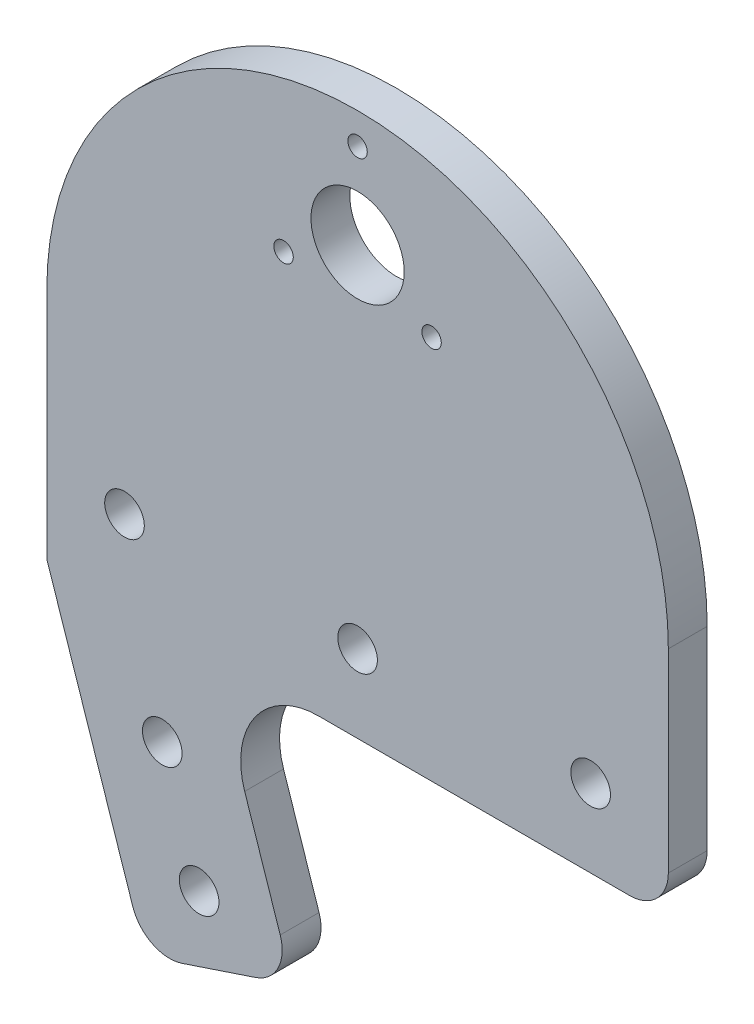
SolidWorks part; units mm, degrees
ref_plane "正面" through (0, 0, 0) normal (0, 0, 1) x (1, 0, 0)
ref_plane "平面" through (0, 0, 0) normal (0, 1, 0) x (1, 0, 0)
ref_plane "右側面" through (0, 0, 0) normal (1, 0, 0) x (0, 0, -1)
sketch "ｽｹｯﾁ1" plane through (0, 0, 0) normal (0, 0, 1) x (1, 0, 0)
  line L0 (-40, -55) -> (40, -55)
  line L1 (-40, -25) -> (-40, -55)
  line L2 (40, -25) -> (40, -55)
  line L3 (0, 0) -> (0, -25) construction
  line L4 (-30, -25) -> (-30, -45) construction
  line L5 (-30, -45) -> (30, -45) construction
  line L6 (30, -45) -> (30, -25) construction
  line L7 (-40, -25) -> (40, -25) construction
  circle A0 centre (0, 0) radius 6
  arc A2 (-40, -25) -> (40, -25) centre (0, -25) cw
  circle A3 centre (-30, -45) radius 2.55
  circle A4 centre (0, -45) radius 2.55
  circle A5 centre (30, -45) radius 2.55
  dimension "D1" = 80
  dimension "D2" = 12
  dimension "D3" = 30
  dimension "D4" = 25
  dimension "D8" = 5.1
  dimension "D5" = 10
  dimension "D6" = 10
  dimension "D7" = 10
extrude "ﾎﾞｽ - 押し出し1" add sketch "ｽｹｯﾁ1" along normal blind 5
sketch "ｽｹｯﾁ2" plane through (0, 0, 5) normal (0, 0, 1) x (1, 0, 0)
  line L0 (-27.3509, -92.9473) -> (-40, -55)
  line L1 (-37.8918, -61.3246) -> (0.0555, -175.1666) construction
  line L2 (-27.3509, -92.9473) -> (-8.3772, -86.6228)
  line L3 (-18.9181, -55) -> (19.0292, -168.842) construction
  line L4 (-8.3772, -86.6228) -> (-18.9181, -55)
  line L5 (-40, -55) -> (40, -55) construction
  line L6 (-18.9181, -55) -> (-20.3412, -55.4743) construction
  line L7 (-18.9181, -55) -> (-40, -55)
  line L8 (-17.8641, -89.7851) -> (-29.4591, -55) construction
  circle A0 centre (-20.3939, -82.1956) radius 2.55
  circle A1 centre (-25.1373, -67.9653) radius 2.55
  dimension "D1" = 8
  dimension "D2" = 5.1
  dimension "D4" = 15
  dimension "D3" = 40
extrude "ﾎﾞｽ - 押し出し2" add sketch "ｽｹｯﾁ2" against normal up to surface (5 mm away) up to face at (-27.45, -45, 0)
fillet "ﾌｨﾚｯﾄ1" radius 10 1 edges at (-18.9181, -55, 2.5)
fillet "ﾌｨﾚｯﾄ2" radius 5 3 edges at (40, -55, 2.5) (-8.3772, -86.6228, 2.5) (-27.3509, -92.9473, 2.5)
sketch "ｽｹｯﾁ3" plane through (0, 0, 5) normal (0, 0, 1) x (1, 0, 0)
  line L0 (0, 0) -> (0, 11) construction
  circle A0 centre (0, 11) radius 1.25
  circle A1 centre (9.5263, -5.5) radius 1.25
  circle A2 centre (-9.5263, -5.5) radius 1.25
  dimension "D1" = 11
  dimension "D2" = 2.5
  dimension "D3" = 3
extrude "ｶｯﾄ - 押し出し1" cut sketch "ｽｹｯﾁ3" against normal through all
